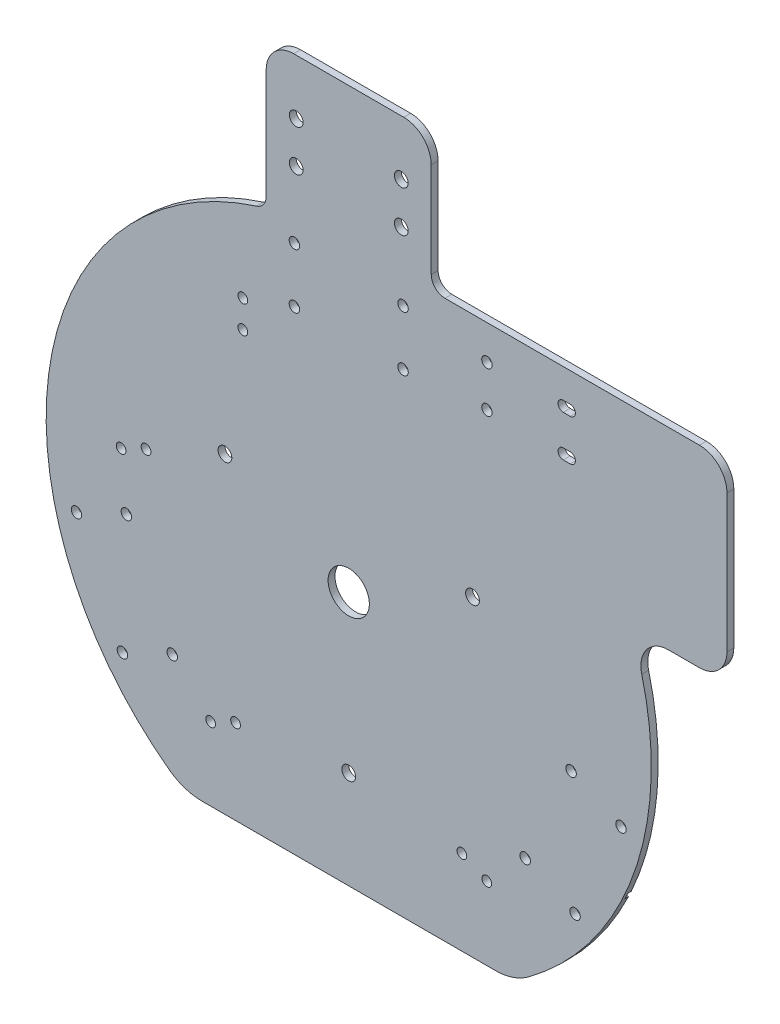
SolidWorks part; units mm, degrees
ref_plane "Front Plane" through (0, 0, 0) normal (0, 0, 1) x (1, 0, 0)
ref_plane "Top Plane" through (0, 0, 0) normal (0, 1, 0) x (1, 0, 0)
ref_plane "Right Plane" through (0, 0, 0) normal (1, 0, 0) x (0, 0, -1)
sketch "Sketch1" plane through (0, 0, 0) normal (0, 0, 1) x (1, 0, 0)
  line L0 (0, 139.7) -> (139.7, 139.7)
  line L2 (139.7, 139.7) -> (174.625, 139.7)
  line L3 (174.625, 139.7) -> (174.625, 50.7007)
  line L4 (174.625, 50.7007) -> (130.175, 50.7007)
  arc A0 (0, 139.7) -> (130.175, 50.7007) centre (0, 0) ccw
  dimension "D1" = 279.4
  dimension "D2" = 139.7
  dimension "D3" = 34.925
  dimension "D4" = 44.45
extrude "Boss-Extrude1" add sketch "Sketch1" along normal blind 3.175
sketch "Sketch2" plane through (0, 0, 0) normal (0, 0, -1) x (-1, 0, 0)
  line L0 (0, -139.7) -> (0, 139.7) construction
  line L1 (-139.7, 0) -> (139.7, 0) construction
  line L2 (-126.6112, -59.0398) -> (-126.6112, 0) construction
  line L3 (126.6112, -59.0398) -> (126.6112, 0) construction
  line L4 (-57.15, 26.6495) -> (0, -72.3372) construction
  line L5 (-126.6112, -59.0398) -> (126.6112, 59.0398) construction
  line L6 (126.6112, -59.0398) -> (-126.6112, 59.0398) construction
  line L7 (-125.9403, -60.4785) -> (127.2821, 57.601)
  line L8 (127.2821, -57.601) -> (-125.9403, 60.4785)
  line L9 (1.5875, -139.7) -> (1.5875, 139.7)
  line L10 (-127.2821, -57.601) -> (125.9403, 60.4785)
  line L11 (125.9403, -60.4785) -> (-127.2821, 57.601)
  line L12 (-1.5875, -139.7) -> (-1.5875, 139.7)
  line L13 (0, -72.3372) -> (57.15, 26.6495) construction
  line L14 (57.15, 26.6495) -> (-57.15, 26.6495) construction
  line L15 (0, 139.7) -> (-174.625, 139.7)
  line L16 (0, 139.7) -> (-174.625, 139.7)
  line L17 (-174.625, 139.7) -> (-174.625, 50.7007)
  line L19 (-121.527, -54.9174) -> (-120.1852, -57.7949)
  line L20 (-120.1852, 57.7949) -> (-121.527, 54.9174)
  line L21 (120.1852, 57.7949) -> (121.527, 54.9174)
  line L22 (-174.625, 139.7) -> (-174.625, 50.7007)
  line L23 (-174.625, 50.7007) -> (-130.175, 50.7007)
  line L24 (-174.625, 50.7007) -> (-130.175, 50.7007)
  line L25 (121.527, -54.9174) -> (120.1852, -57.7949)
  line L26 (-1.5875, 133.35) -> (1.5875, 133.35)
  circle A0 centre (0, 0) radius 139.7 construction
  arc A2 (-130.175, 50.7007) -> (0, 139.7) centre (0, 0) ccw
  arc A3 (-130.175, 50.7007) -> (0, 139.7) centre (0, 0) ccw
  circle A4 centre (-57.15, 26.6495) radius 3.175
  circle A5 centre (57.15, 26.6495) radius 3.175
  circle A6 centre (0, -72.3372) radius 3.175
  point P6 (0, 0)
  point P11 (0, 0)
  arc M9 (-130.175, 50.7007) -> (0, 139.7) centre (0, 0) ccw
  line M24 (0, 139.7) -> (-174.625, 139.7)
  dimension "D5" = 6.35
  dimension "D1" = 25
  dimension "D6" = 114.3
  dimension "D7" = 6.35
  dimension "D8" = 6.35
  dimension "D9" = 6.35
  dimension "D10" = 6.35
  dimension "D11" = 6.35
  dimension "D2" = 1.5875
  dimension "D3" = 1.5875
  dimension "D4" = 0
extrude "Cut-Extrude3" cut sketch "Sketch2" against normal blind 1.5875 contours L12 L7 L11 | L12 L11 L7 L9 L8 L10 | L11 L9 L7 | L11 L12 L10 | L12 L10 L8 | L10 L8 L9 | L9 L7 L8 | L19 L10 L7 M9 | L10 L21 L7 M9 | L8 L25 L11 M9 | L12 L26 L9 M9 M24 region at (123.7323, -57.6973, 0) region at (1.0583, -1.7516, 0) region at (0, 0, 0) region at (-1.0583, -1.7516, 0) region at (2.3104, 0, 0) region at (-123.7323, -57.6973, 0) region at (-2.3104, 0, 0) region at (1.0583, 1.7516, 0) region at (-1.0583, 1.7516, 0) region at (0.0003, 136.5242, 0) region at (-123.7323, 57.6973, 0)
sketch "Sketch3" plane through (0, 0, 3.175) normal (0, 0, 1) x (1, 0, 0)
  circle A0 centre (0, 0) radius 9.525
  dimension "D1" = 19.05
extrude "Cut-Extrude4" cut sketch "Sketch3" against normal through all
extrude "Cut-Extrude5" cut sketch "Sketch2<4>" against normal through all contours L8 A4 L11 | L11 A4 | L8 A4 | L7 A5 L10 | L10 A5 | L7 A5 | L12 A6 | L9 A6 L12 | L9 A6 region at (2.2384, -72.3372, 0) region at (0, -72.3372, 0) region at (-2.2384, -72.3372, 0) region at (58.096, 24.6208, 0) region at (57.15, 26.6495, 0) region at (-57.15, 26.6495, 0) region at (-58.096, 24.6208, 0) region at (56.204, 28.6782, 0) region at (-56.204, 28.6782, 0)
sketch "Sketch2<4>" plane through (0, 0, 0) normal (0, 0, -1) x (-1, 0, 0) same geometry as "Sketch2"
sketch "Sketch4" plane through (0, 0, 3.175) normal (0, 0, 1) x (1, 0, 0)
  line L0 (86.721, 139.7) -> (86.721, 88.9)
  line L1 (86.721, 88.9) -> (139.7, 88.9)
  line L2 (130.175, 50.7007) -> (174.625, 50.7007)
  line L3 (174.625, 139.7) -> (0, 139.7)
  line L5 (174.625, 139.7) -> (0, 139.7)
  line L9 (130.175, 50.7007) -> (174.625, 50.7007)
  line L10 (174.625, 50.7007) -> (174.625, 139.7)
  line L11 (174.625, 50.7007) -> (174.625, 139.7)
  arc A3 (0, 139.7) -> (130.175, 50.7007) centre (0, 0) ccw
  arc A5 (0, 139.7) -> (130.175, 50.7007) centre (0, 0) ccw
  dimension "D3" = 50.8
  dimension "D1" = 0
sketch "Sketch8" plane through (0, 0, 3.175) normal (0, 0, 1) x (1, 0, 0)
  circle A0 centre (25.0825, 101.6) radius 2.413 construction
  circle A1 centre (-25.0825, 101.6) radius 2.413 construction
  circle A2 centre (-25.0825, 127) radius 2.413 construction
  circle A3 centre (25.0825, 127) radius 2.413 construction
  circle A4 centre (102.6812, -20.2056) radius 2.413 construction
  circle A5 centre (125.7014, -30.9401) radius 2.413 construction
  circle A6 centre (81.4805, -65.6705) radius 2.413 construction
  circle A7 centre (104.5008, -76.405) radius 2.413 construction
  circle A8 centre (-81.4805, -65.6705) radius 2.413 construction
  circle A9 centre (-104.5008, -76.405) radius 2.413 construction
  circle A10 centre (-102.6812, -20.2056) radius 2.413 construction
  circle A11 centre (-125.7014, -30.9401) radius 2.413 construction
  circle A12 centre (25.0825, 101.6) radius 2.413
  circle A13 centre (-25.0825, 101.6) radius 2.413
  circle A14 centre (-25.0825, 127) radius 2.413
  circle A15 centre (25.0825, 127) radius 2.413
  circle A16 centre (102.6812, -20.2056) radius 2.413
  circle A17 centre (125.7014, -30.9401) radius 2.413
  circle A18 centre (81.4805, -65.6705) radius 2.413
  circle A19 centre (104.5008, -76.405) radius 2.413
  circle A20 centre (-81.4805, -65.6705) radius 2.413
  circle A21 centre (-104.5008, -76.405) radius 2.413
  circle A22 centre (-102.6812, -20.2056) radius 2.413
  circle A23 centre (-125.7014, -30.9401) radius 2.413
extrude "Cut-Extrude7" cut sketch "Sketch8" against normal through all
sketch "Sketch9" plane through (0, 0, 3.175) normal (0, 0, 1) x (1, 0, 0)
  line L0 (102.235, 123.825) -> (99.06, 123.825) construction
  line L1 (102.235, 121.412) -> (99.06, 121.412)
  line L2 (102.235, 126.238) -> (99.06, 126.238)
  line L3 (100.6475, 123.825) -> (100.6475, 104.775) construction
  line L4 (100.6475, 114.3) -> (63.8175, 114.3) construction
  line L6 (102.235, 104.775) -> (99.06, 104.775) construction
  line L7 (102.235, 107.188) -> (99.06, 107.188)
  line L8 (102.235, 102.362) -> (99.06, 102.362)
  circle A2 centre (100.6475, 104.775) radius 2.413 construction
  circle A3 centre (100.6475, 123.825) radius 2.413 construction
  circle A4 centre (63.8175, 104.775) radius 2.413 construction
  circle A5 centre (63.8175, 123.825) radius 2.413 construction
  circle A8 centre (100.6475, 104.775) radius 2.413
  circle A9 centre (100.6475, 123.825) radius 2.413
  circle A10 centre (63.8175, 104.775) radius 2.413
  circle A11 centre (63.8175, 123.825) radius 2.413
  arc A12 (102.235, 121.412) -> (102.235, 126.238) centre (102.235, 123.825) ccw
  arc A13 (99.06, 126.238) -> (99.06, 121.412) centre (99.06, 123.825) ccw
  arc A14 (102.235, 107.188) -> (102.235, 102.362) centre (102.235, 104.775) cw
  arc A15 (99.06, 102.362) -> (99.06, 107.188) centre (99.06, 104.775) cw
  point P20 (100.6475, 123.825)
  point P29 (100.6475, 104.775)
  dimension "D1" = 4.826
  dimension "D2" = 3.175
extrude "Cut-Extrude8" cut sketch "Sketch9" against normal through all contours A9 | A11 | A10 | A8 | L2 A13 L1 A9 | L1 A12 L2 A9 | A15 L8 A8 L7 | A14 L7 A8 L8 region at (103.3364, 123.825, 3.175) region at (97.9586, 123.825, 3.175) region at (100.6475, 123.825, 3.175) region at (103.3364, 104.775, 3.175) region at (97.9586, 104.775, 3.175) region at (100.6475, 104.775, 3.175) region at (63.8175, 104.775, 3.175) region at (63.8175, 123.825, 3.175)
fillet "Fillet1" radius 12.7 3 edges at (174.625, 50.7007, 1.5875) (174.625, 139.7, 1.5875) (130.175, 50.7007, 1.5875)
sketch "Sketch10" plane through (0, 0, 3.175) normal (0, 0, 1) x (1, 0, 0)
  line L0 (-75.6023, -117.475) -> (75.6023, -117.475)
  line L3 (147.5863, 50.7007) -> (161.925, 50.7007)
  line L4 (174.625, 63.4007) -> (174.625, 127)
  line L5 (161.925, 139.7) -> (0, 139.7)
  line L6 (147.5863, 50.7007) -> (161.925, 50.7007)
  line L7 (174.625, 63.4007) -> (174.625, 127)
  line L8 (161.925, 139.7) -> (0, 139.7)
  arc A4 (161.925, 50.7007) -> (174.625, 63.4007) centre (161.925, 63.4007) ccw
  arc A5 (174.625, 127) -> (161.925, 139.7) centre (161.925, 127) ccw
  arc A6 (0, 139.7) -> (135.2874, 34.834) centre (0, 0) ccw
  arc A7 (147.5863, 50.7007) -> (135.2874, 34.834) centre (147.5863, 38.0007) ccw
  arc A8 (161.925, 50.7007) -> (174.625, 63.4007) centre (161.925, 63.4007) ccw
  arc A9 (174.625, 127) -> (161.925, 139.7) centre (161.925, 127) ccw
  arc A10 (0, 139.7) -> (135.2874, 34.834) centre (0, 0) ccw
  arc A11 (147.5863, 50.7007) -> (135.2874, 34.834) centre (147.5863, 38.0007) ccw
  arc M36 (0, 139.7) -> (135.2874, 34.834) centre (0, 0) ccw
  dimension "D2" = 117.475
  dimension "D1" = 0
extrude "Cut-Extrude9" cut sketch "Sketch10" against normal through all contours L0 M36 region at (0, -126.4285, 3.175)
fillet "Fillet2" radius 25.4 2 edges at (75.6023, -117.475, 1.5875) (-75.6023, -117.475, 1.5875)
sketch "Sketch11" plane through (0, 0, 3.175) normal (0, 0, 1) x (1, 0, 0)
  circle A0 centre (52.2526, -78.3155) radius 2.032 construction
  circle A1 centre (63.7627, -83.6827) radius 2.032 construction
  circle A2 centre (-48.895, 80.4545) radius 2.032 construction
  circle A3 centre (-48.895, 93.1545) radius 2.032 construction
  circle A4 centre (-63.7627, -83.6827) radius 2.032 construction
  circle A5 centre (-52.2526, -78.3155) radius 2.032 construction
  circle A6 centre (-105.0906, 4.9451) radius 2.032 construction
  circle A7 centre (-93.5805, 10.3124) radius 2.032 construction
  circle A8 centre (52.2526, -78.3155) radius 2.032 construction
  circle A9 centre (63.7627, -83.6827) radius 2.032 construction
  circle A10 centre (-48.895, 80.4545) radius 2.032 construction
  circle A11 centre (-48.895, 93.1545) radius 2.032 construction
  circle A12 centre (-63.7627, -83.6827) radius 2.032 construction
  circle A13 centre (-52.2526, -78.3155) radius 2.032 construction
  circle A14 centre (-105.0906, 4.9451) radius 2.032 construction
  circle A15 centre (-93.5805, 10.3124) radius 2.032 construction
  circle A16 centre (-93.5805, 10.3124) radius 2.2479
  circle A17 centre (-105.0906, 4.9451) radius 2.2479
  circle A18 centre (-52.2526, -78.3155) radius 2.2479
  circle A19 centre (-63.7627, -83.6827) radius 2.2479
  circle A20 centre (52.2526, -78.3155) radius 2.2479
  circle A21 centre (63.7627, -83.6827) radius 2.2479
  circle A22 centre (-48.895, 93.1545) radius 2.2479
  circle A23 centre (-48.895, 80.4545) radius 2.2479
  dimension "D1" = 4.4958
extrude "Cut-Extrude10" cut sketch "Sketch11" against normal through all
sketch "Sketch12" plane through (0, 0, 0) normal (0, 0, -1) x (-1, 0, 0)
  line L0 (0, 0) -> (0, 50000) construction
  line L1 (-24.257, 9.525) -> (24.257, 9.525) construction
  line L2 (-24.257, 9.525) -> (-24.257, -9.525) construction
  line L3 (-24.257, -9.525) -> (24.257, -9.525) construction
  line L4 (24.257, 9.525) -> (24.257, -9.525) construction
  line L5 (-24.257, 9.525) -> (24.257, -9.525) construction
  line L6 (-24.257, -9.525) -> (24.257, 9.525) construction
  line L22 (-67.7251, -117.475) -> (67.7251, -117.475)
  line L23 (125.9321, -60.4747) -> (120.1852, -57.7949)
  line L24 (120.1852, -57.7949) -> (121.527, -54.9174)
  line L25 (121.527, -54.9174) -> (127.2739, -57.5972)
  line L26 (127.2739, 57.5972) -> (121.527, 54.9174)
  line L27 (121.527, 54.9174) -> (120.1852, 57.7949)
  line L28 (120.1852, 57.7949) -> (125.9321, 60.4747)
  line L29 (1.5875, 139.691) -> (1.5875, 133.35)
  line L30 (1.5875, 133.35) -> (-1.5875, 133.35)
  line L31 (-1.5875, 133.35) -> (-1.5875, 139.7)
  line L32 (-1.5875, 139.7) -> (-161.925, 139.7)
  line L33 (-174.625, 127) -> (-174.625, 63.4007)
  line L34 (-161.925, 50.7007) -> (-147.5863, 50.7007)
  line L35 (-127.2739, -57.5972) -> (-121.527, -54.9174)
  line L36 (-121.527, -54.9174) -> (-120.1852, -57.7949)
  line L37 (-120.1852, -57.7949) -> (-125.9321, -60.4747)
  line L38 (-67.7251, -117.475) -> (67.7251, -117.475)
  line L39 (125.9321, -60.4747) -> (120.1852, -57.7949)
  line L40 (120.1852, -57.7949) -> (121.527, -54.9174)
  line L41 (121.527, -54.9174) -> (127.2739, -57.5972)
  line L42 (127.2739, 57.5972) -> (121.527, 54.9174)
  line L43 (121.527, 54.9174) -> (120.1852, 57.7949)
  line L44 (120.1852, 57.7949) -> (125.9321, 60.4747)
  line L45 (1.5875, 139.691) -> (1.5875, 133.35)
  line L46 (1.5875, 133.35) -> (-1.5875, 133.35)
  line L47 (-1.5875, 133.35) -> (-1.5875, 139.7)
  line L48 (-1.5875, 139.7) -> (-161.925, 139.7)
  line L49 (-174.625, 127) -> (-174.625, 63.4007)
  line L50 (-161.925, 50.7007) -> (-147.5863, 50.7007)
  line L51 (-127.2739, -57.5972) -> (-121.527, -54.9174)
  line L52 (-121.527, -54.9174) -> (-120.1852, -57.7949)
  line L53 (-120.1852, -57.7949) -> (-125.9321, -60.4747)
  circle A0 centre (-24.257, 9.525) radius 3.175
  circle A1 centre (24.257, 9.525) radius 3.175
  circle A2 centre (24.257, -9.525) radius 3.175
  circle A3 centre (-24.257, -9.525) radius 3.175
  arc A14 (-125.9321, -60.4747) -> (-82.7751, -112.5361) centre (0, 0) ccw
  arc A15 (-82.7751, -112.5361) -> (-67.7251, -117.475) centre (-67.7251, -92.075) ccw
  arc A16 (67.7251, -117.475) -> (82.7751, -112.5361) centre (67.7251, -92.075) ccw
  arc A17 (82.7751, -112.5361) -> (125.9321, -60.4747) centre (0, 0) ccw
  arc A18 (127.2739, -57.5972) -> (127.2739, 57.5972) centre (0, 0) ccw
  arc A19 (125.9321, 60.4747) -> (1.5875, 139.691) centre (0, 0) ccw
  arc A20 (-161.925, 139.7) -> (-174.625, 127) centre (-161.925, 127) ccw
  arc A21 (-174.625, 63.4007) -> (-161.925, 50.7007) centre (-161.925, 63.4007) ccw
  arc A22 (-135.2874, 34.834) -> (-147.5863, 50.7007) centre (-147.5863, 38.0007) ccw
  arc A23 (-135.2874, 34.834) -> (-127.2739, -57.5972) centre (0, 0) ccw
  arc A24 (-125.9321, -60.4747) -> (-82.7751, -112.5361) centre (0, 0) ccw
  arc A25 (-82.7751, -112.5361) -> (-67.7251, -117.475) centre (-67.7251, -92.075) ccw
  arc A26 (67.7251, -117.475) -> (82.7751, -112.5361) centre (67.7251, -92.075) ccw
  arc A27 (82.7751, -112.5361) -> (125.9321, -60.4747) centre (0, 0) ccw
  arc A28 (127.2739, -57.5972) -> (127.2739, 57.5972) centre (0, 0) ccw
  arc A29 (125.9321, 60.4747) -> (1.5875, 139.691) centre (0, 0) ccw
  arc A30 (-161.925, 139.7) -> (-174.625, 127) centre (-161.925, 127) ccw
  arc A31 (-174.625, 63.4007) -> (-161.925, 50.7007) centre (-161.925, 63.4007) ccw
  arc A32 (-135.2874, 34.834) -> (-147.5863, 50.7007) centre (-147.5863, 38.0007) ccw
  arc A33 (-135.2874, 34.834) -> (-127.2739, -57.5972) centre (0, 0) ccw
  point P0 (0, 0)
  dimension "D3" = 6.35
  dimension "D1" = 48.514
  dimension "D2" = 19.05
  dimension "D4" = 0
sketch "Sketch14" plane through (0, 0, 0) normal (0, 0, -1) x (-1, 0, 0)
  line L0 (0, 0) -> (0, 50000) construction
  line L1 (-38.1, 139.7) -> (-38.1, 202.565)
  line L2 (-161.925, 139.7) -> (-1.5875, 139.7) construction
  line L3 (-38.1, 202.565) -> (38.1, 202.565)
  line L4 (38.1, 202.565) -> (38.1, 134.4042)
  line L6 (-24.257, 177.165) -> (24.257, 177.165) construction
  line L7 (-24.257, 177.165) -> (-24.257, 158.115) construction
  line L8 (-24.257, 158.115) -> (24.257, 158.115) construction
  line L9 (24.257, 177.165) -> (24.257, 158.115) construction
  line L10 (-24.257, 177.165) -> (24.257, 158.115) construction
  line L11 (-24.257, 158.115) -> (24.257, 177.165) construction
  line L12 (-38.1, 139.7) -> (0, 139.7)
  arc A0 (125.9321, 60.4747) -> (1.5875, 139.691) centre (0, 0) ccw construction
  circle A1 centre (-24.257, 177.165) radius 3.175
  circle A2 centre (24.257, 177.165) radius 3.175
  circle A3 centre (24.257, 158.115) radius 3.175
  circle A4 centre (-24.257, 158.115) radius 3.175
  arc A5 (38.1, 134.4042) -> (0, 139.7) centre (0, 0) ccw
  point P7 (0, 202.565)
  point P13 (0, 167.64)
  dimension "D6" = 6.35
  dimension "D1" = 76.2
  dimension "D2" = 48.514
  dimension "D3" = 19.05
  dimension "D4" = 167.64
  dimension "D5" = 25.4
extrude "Boss-Extrude2" add sketch "Sketch14" against normal up to surface (3.175 mm away) up to face at (54.5005, -78.3155, 3.175)
fillet "Fillet3" radius 12.7 2 edges at (-38.1, 202.565, 1.5875) (38.1, 202.565, 1.5875)
fillet "Fillet4" radius 6.35 2 edges at (-38.1, 134.4042, 1.5875) (38.1, 139.7, 1.5875)
